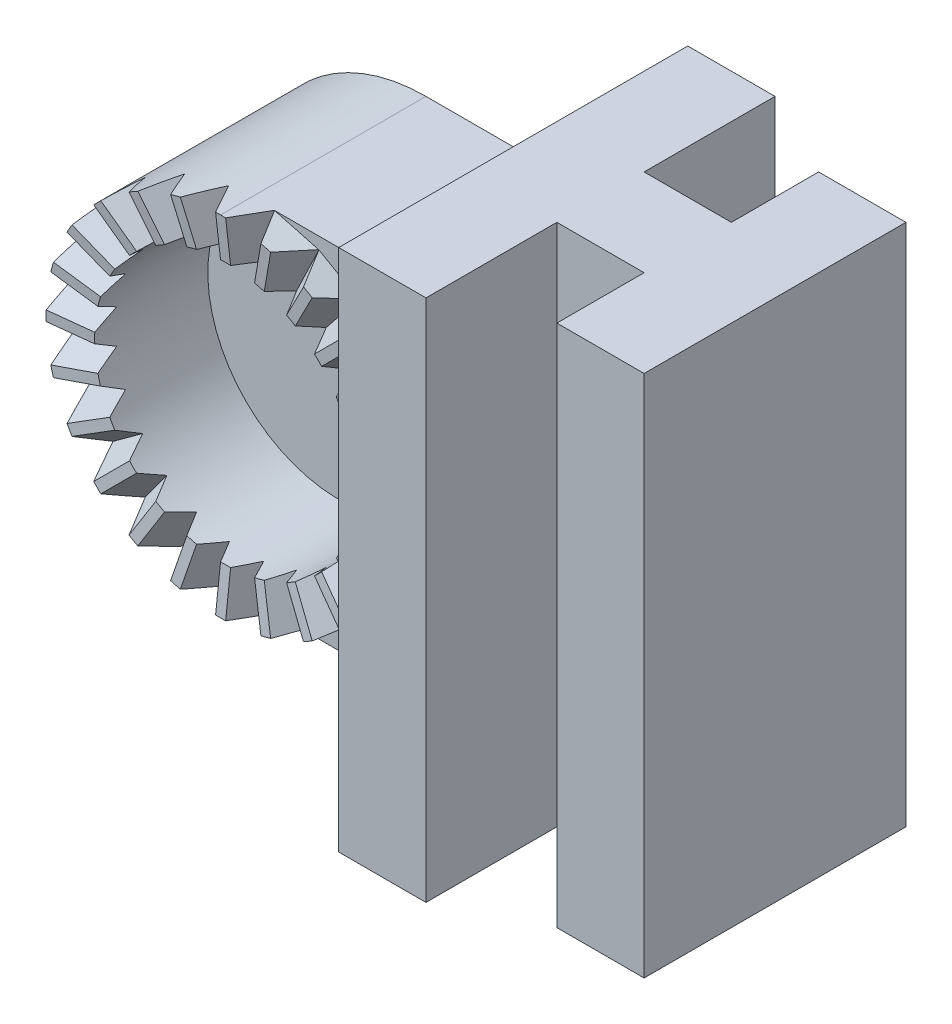
SolidWorks part; units mm, degrees
ref_plane "Front Plane" through (0, 0, 0) normal (0, 0, 1) x (1, 0, 0)
ref_plane "Top Plane" through (0, 0, 0) normal (0, 1, 0) x (1, 0, 0)
ref_plane "Right Plane" through (0, 0, 0) normal (1, 0, 0) x (0, 0, -1)
sketch "Sketch2" plane through (0, 0, 0) normal (0, 0, 1) x (1, 0, 0)
  line L0 (20, 20) -> (20, -10)
  line L1 (20, -10) -> (0, -10)
  line L2 (20, 20) -> (15, 20)
  line L3 (15, 20) -> (15, 10)
  line L4 (15, 10) -> (0, 10)
  line L5 (15, 10) -> (15, -10)
  circle A1 centre (0, 0) radius 10
  point P9 (0, 0)
  point P10 (0, 0)
  dimension "D1" = 20
  dimension "D2" = 30
  dimension "D3" = 5
  dimension "D4" = 15
extrude "Boss-Extrude1" add sketch "Sketch2" along normal blind 20 contours A1 L1 L0 L2 L3 L4 region at (17.5, 5, 0)
sketch "Sketch3" plane through (0, -10, 0) normal (0, -1, 0) x (1, 0, 0)
  line L0 (20, 12.5) -> (25, 12.5)
  line L1 (20, 20) -> (20, 0) construction
  line L2 (25, 12.5) -> (25, 17.5)
  line L3 (25, 17.5) -> (30, 17.5)
  line L4 (30, 17.5) -> (30, 2.5)
  line L5 (30, 2.5) -> (25, 2.5)
  line L6 (25, 2.5) -> (25, 7.5)
  line L7 (25, 7.5) -> (20, 7.5)
  line L8 (20, 7.5) -> (20, 12.5)
  point P4 (20, 10)
  dimension "D1" = 5
  dimension "D2" = 5
  dimension "D3" = 5
extrude "Boss-Extrude2" add sketch "Sketch3" against normal up to surface (30 mm away) up to face at (17.5, 20, 10)
extrude "Boss-Extrude3" add sketch "Sketch2<3>" along normal blind 10 contours A1 | A1 L5 L4 | A1 L1 L5 region at (11.0784, 0, 0) region at (0, 0, 0)
sketch "Sketch2<3>" plane through (0, 0, 0) normal (0, 0, 1) x (1, 0, 0) same geometry as "Sketch2"
sketch "Sketch4" plane through (0, 0, 10) normal (0, 0, 1) x (1, 0, 0)
  line L0 (0, 0) -> (-6.8443, 7.2908)
  line L2 (-8.4981, 5.271) -> (0, 0)
  circle A0 centre (0, 0) radius 7.5
  circle A1 centre (0, 0) radius 10
  arc A2 (0, 10) -> (0, -10) centre (0, 0) ccw construction
  point P2 (0, 0)
  point P10 (0, 0)
  dimension "D1" = 15
  dimension "D2" = 15
  dimension "D3" = 0
extrude "Cut-Extrude3" cut sketch "Sketch4" against normal blind 5 and the other way blind 10 contours L2 A0 L0 | L0 A0 L2 region at (-3.8576, 3.1585, 10) region at (0.1677, -0.1373, 10)
ref_plane "Plane1" through (-10, 0, 0) normal (-1, 0, 0) x (0, 0, 1)
sketch "Sketch5" plane through (-10, 0, 0) normal (-1, 0, 0) x (0, 0, 1)
  line L0 (12.267, 0) -> (10, 1.3089)
  line L1 (10, -10) -> (10, 10) construction
  line L2 (10, 1.3089) -> (10, -1.3089)
  line L3 (10, -1.3089) -> (12.267, 0)
  point P6 (10, 0)
  dimension "D1" = 60
  dimension "D2" = 2.267
ref_axis "Axis1" through (0, 0, 31.9434) along (0, 0, -1)
ref_plane "Plane2" through (-5, 0, 0) normal (-1, 0, 0) x (0, 0, 1)
sketch "Sketch6" plane through (-5, 0, 0) normal (-1, 0, 0) x (0, 0, 1)
  line L0 (10, 0.9815) -> (10, -0.9815)
  line L1 (10, 1.3089) -> (10, -1.3089) construction
  line L2 (10, -0.9815) -> (11.7, 0)
  line L3 (31.9434, 0) -> (5, 0) construction
  line L4 (11.7, 0) -> (10, 0.9815)
  point P4 (0, 0)
  dimension "D1" = 60
  dimension "D2" = 1.7
sketch3d "3DSketch1"
  line L0 (-10, 0, 12.267) -> (-5, 0, 11.7)
  line L1 (-10, -1.3089, 10) -> (-5, -0.9815, 10)
  line L2 (-10, 1.3089, 10) -> (-5, 0.9815, 10)
  line L3 (-10, 1.3089, 10) -> (-10, -1.3089, 10) construction
loft "Loft1" add profiles "Sketch5", "Sketch6" connector at (-10, 0, 12.267) connector at (-5, 0, 11.7)
pattern_circular "CirPattern5" count 24 over 360 about axis through (0, 0, 31.9434) along (0, 0, -1) of "Loft1"
extrude "Cut-Extrude4" cut sketch "Sketch4<6>" along normal blind 10 contours L0 A0 L2 | L2 A0 L0 region at (-3.8576, 3.1585, 10) region at (0.1677, -0.1373, 10)
sketch "Sketch4<6>" plane through (0, 0, 10) normal (0, 0, 1) x (1, 0, 0) same geometry as "Sketch4"
sketch "Sketch9" plane through (0, 0, 0) normal (0, 0, 1) x (1, 0, 0)
  line L0 (0, 10) -> (0, 11)
  line L1 (0, -10) -> (0, -11)
  arc A0 (0, -10) -> (0, 10) centre (0, 0) cw
  arc A1 (0, 11) -> (0, -11) centre (0, 0) ccw
  dimension "D1" = 1
extrude "Cut-Extrude5" cut sketch "Sketch9" along normal blind 20
sketch "Sketch12" plane through (0, 0, 0) normal (0, 1, 0) x (1, 0, 0)
  line L0 (-7.3585, -11.4675) -> (-10.6014, -11.8352)
  line L1 (-10, -12.267) -> (-5, -11.7) construction
  line L4 (-7.3585, -11.9675) -> (-7.3585, -11.4675)
  line L7 (-7.3585, -11.9675) -> (-10.6419, -12.3398)
  line L8 (-10.6419, -12.3398) -> (-10.6014, -11.8352)
  point P5 (-10, -12.267)
  point P7 (-10.6519, -12.2376)
  dimension "1" = 0.5
revolve "Cut-Revolve2" cut sketch "Sketch12" angle 360 about axis through (0, 0, 31.9434) along (0, 0, -1) region at (-8.9901, 0, 11.903)
